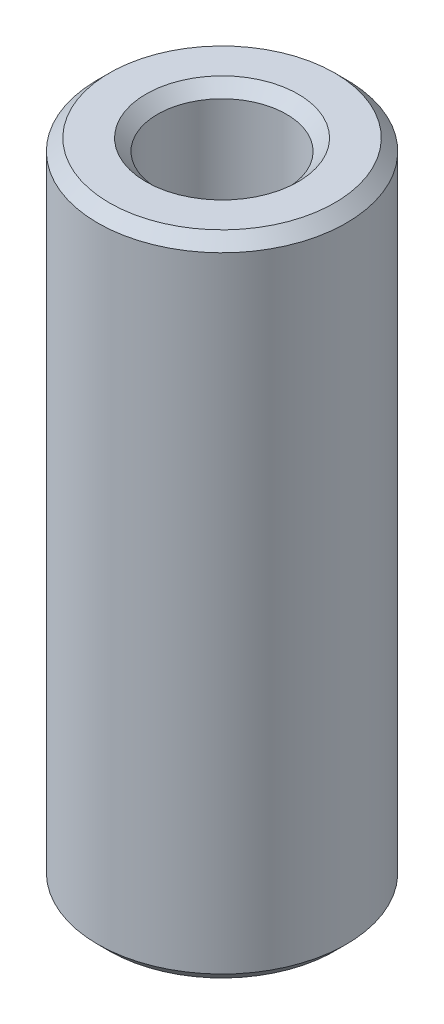
SolidWorks part; units mm, degrees
ref_plane "Front Plane" through (0, 0, 0) normal (0, 0, 1) x (1, 0, 0)
ref_plane "Top Plane" through (0, 0, 0) normal (0, 1, 0) x (1, 0, 0)
ref_plane "Right Plane" through (0, 0, 0) normal (1, 0, 0) x (0, 0, -1)
sketch "Sketch1" plane through (0, 0, 0) normal (0, 1, 0) x (1, 0, 0)
  circle A0 centre (0, 0) radius 42.5
  dimension "SLEEVE_OD" = 85
extrude "Boss-Extrude1" add sketch "Sketch1" along normal blind 221.6331
sketch "Sketch2" plane through (0, 0, 0) normal (0, 1, 0) x (1, 0, 0)
  circle A0 centre (0, 0) radius 22.0341
  dimension "BORE_D" = 44.0682
extrude "Cut-Extrude1" cut sketch "Sketch2" along normal through all
chamfer "Chamfer1" distance 3.9804 angle 45 4 edges at (0, 221.6331, 22.0341) (0, 0, 22.0341) (0, 0, 42.5) (0, 221.6331, 42.5)
